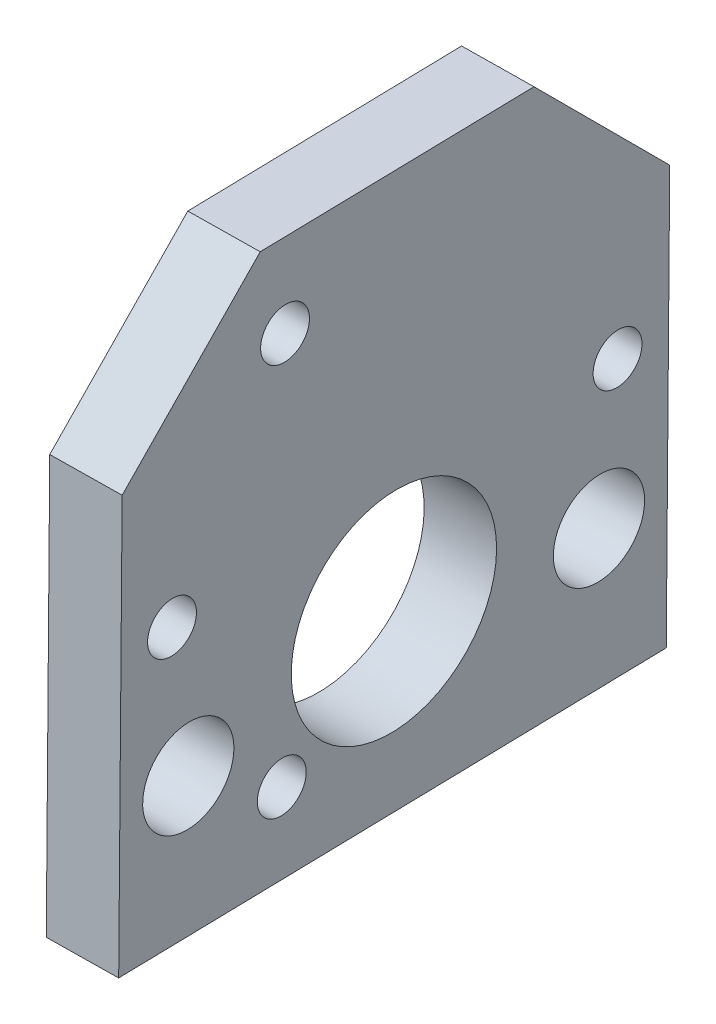
SolidWorks part; units mm, degrees
material "1060 Alloy"
ref_plane "Front" through (0, 0, 0) normal (0, 0, 1) x (1, 0, 0)
ref_plane "Top" through (0, 0, 0) normal (0, 1, 0) x (1, 0, 0)
ref_plane "Right" through (0, 0, 0) normal (1, 0, 0) x (0, 0, -1)
sketch "Sketch1" plane through (39.5296, -0.3237, -0.8516) normal (0.9997, -0.0082, -0.0215) x (-0.0215, 0.0001, -0.9998)
  line L1 (-19.05, 19.05) -> (19.05, 19.05)
  line L2 (-19.05, 19.05) -> (-19.05, -19.05)
  line L3 (-19.05, -19.05) -> (19.05, -19.05)
  line L4 (19.05, 19.05) -> (19.05, -19.05)
  line L5 (0, 19.05) -> (0, -19.05) construction
  circle A6 centre (0, -7.112) radius 7.1438
  point P4 (0, 0)
  dimension "D4" = 14.2875
  dimension "D5" = 7.112
  dimension "D1" = 38.1
  dimension "D2" = 19.05
  dimension "D3" = 19.05
extrude "Boss-Extrude1" add sketch "Sketch1" along normal blind 4.826
chamfer "Chamfer1" distance 9.525 angle 45 2 edges at (41.6877, 18.7076, -19.9509) (42.5083, 18.7042, 18.1403)
hole_wizard "M3 Clearance Hole1" positions "Sketch2" profile "Sketch3" hole size "M3" standard "ANSI Metric" end condition through all
sketch "Sketch2" plane through (44.3544, -0.3632, -0.9556) normal (0.9997, -0.0082, -0.0215) x (-0.0215, 0.0001, -0.9998)
  point P5 (15.5, -0.112)
  point P8 (-15.5, -0.112)
  point P11 (-7.75, -13.5354)
  point P14 (-7.75, 13.3114)
sketch "Sketch3" plane through (44.0196, -0.4739, -16.452) normal (0.021, 0.707, 0.707) x (-0.0094, 0.7072, -0.7069)
  line L0 (0, 0) -> (0, 5.9583)
  line L1 (0, 5.9583) -> (1.7, 5.9583)
  line L2 (1.7, 5.9583) -> (1.7, 0)
  line L5 (1.7, 0) -> (0, 0)
  line L11 (0, -6.35) -> (0, 107.95) construction
  dimension "Thru Hole Dia." = 3.4
  dimension "Thru Hole Depth" = 5.9583
hole_wizard "1/4 (0.2500) Dowel Hole1" positions "Sketch4" profile "Sketch6" hole size "1/4" standard "ANSI Inch" end condition through all
sketch "Sketch4" plane through (44.3544, -0.3632, -0.9556) normal (0.9997, -0.0082, -0.0215) x (-0.0215, 0.0002, -0.9998)
  line L0 (-0.0006, 0.0318) -> (-0.0006, -23.774) construction
  line L2 (-19.0517, -19.0483) -> (19.0483, -19.0517) construction
  circle A0 centre (-0.0006, -7.112) radius 7.1438 construction
  point P0 (14.2869, -9.5263)
  point P27 (-14.2881, -9.5263)
  point P38 (0, 0)
  point P39 (0, 0)
  point P40 (13.8287, -7.1132)
  point P42 (0, 0)
  point P43 (0, 0)
  point P44 (12.6994, -11.2109)
  point P45 (-12.7006, -9.9412)
  dimension "D1" = 14.2875
  dimension "D2" = 9.525
sketch "Sketch6" plane through (43.9686, -9.8867, -15.2391) normal (0.021, 0.707, 0.707) x (-0.0094, 0.7072, -0.7069)
  line L0 (0, 0) -> (0, 5.9583)
  line L1 (0, 5.9583) -> (3.175, 5.9583)
  line L2 (3.175, 5.9583) -> (3.175, 0)
  line L5 (3.175, 0) -> (0, 0)
  line L11 (0, -6.35) -> (0, 107.95) construction
  dimension "Thru Hole Dia." = 6.35
  dimension "Thru Hole Depth" = 5.9583
